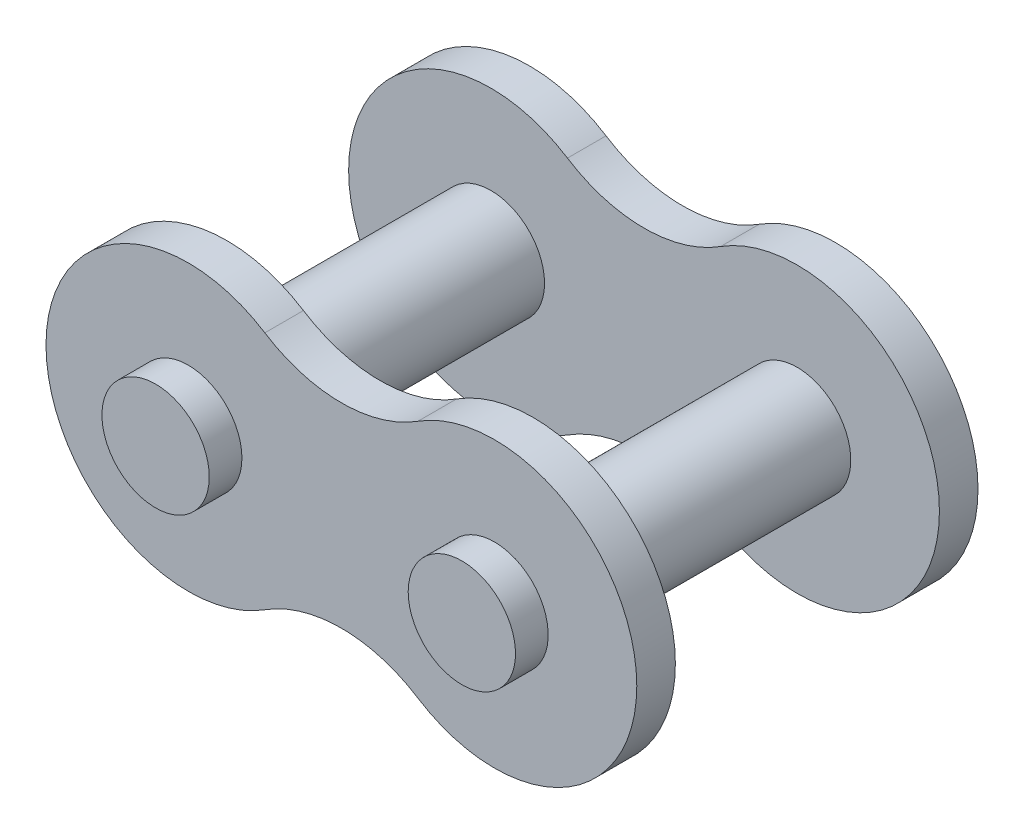
SolidWorks part; units mm, degrees
material "AISI 1020"
ref_plane "Спереди" through (0, 0, 0) normal (0, 0, 1) x (1, 0, 0)
ref_plane "Сверху" through (0, 0, 0) normal (0, 1, 0) x (1, 0, 0)
ref_plane "Справа" through (0, 0, 0) normal (1, 0, 0) x (0, 0, -1)
sketch "Эскиз1" plane through (0, 0, 0) normal (0, 0, 1) x (1, 0, 0)
  line L0 (-1000, 0) -> (49000, 0) construction
  line L1 (0, -1000) -> (0, 49000) construction
  line L2 (0, 4.0457) -> (0, -4.0457)
  circle A0 centre (-6.35, 0) radius 2.225
  arc A1 (-3.175, 4.9729) -> (-3.175, -4.9729) centre (-6.35, 0) ccw
  arc A2 (-3.175, 4.9729) -> (0, 4.0457) centre (0, 9.9457) ccw
  arc A3 (-3.175, -4.9729) -> (0, -4.0457) centre (0, -9.9457) cw
  dimension "_d2_" = 4.45
  dimension "_h2_" = 11.8
  dimension "_P" = 12.7
sketch "Эскиз2" plane through (0, 0, 0) normal (0, 1, 0) x (1, 0, 0)
  line L0 (-2392.2672, 0) -> (117221.091, 0) construction
  line L1 (0, 0) -> (0, 3.875) construction
  line L2 (0, 3.875) -> (0, 5.475) construction
  line L3 (0, 5.475) -> (0, 7.075)
  line L4 (0, 7.075) -> (0, 8.43) construction
  point P5 (0, 0)
  point P9 (0, 0)
  point P10 (0, 0)
  dimension "_b1_" = 7.75
  dimension "_T" = 1.6
  dimension "_L" = 16.86
extrude "Бобышка-Вытянуть1" add sketch "Эскиз1" against normal up to vertex (7.075 mm away) from vertex contours A2 L2 A3 A1 up to point (0, 0, -7.075) starting at point (0, 0, -5.475)
extrude "Бобышка-Вытянуть2" add sketch "Эскиз1<3>" against normal up to vertex (8.43 mm away) contours A0 up to point (0, 0, -8.43)
sketch "Эскиз1<3>" plane through (0, 0, 0) normal (0, 0, 1) x (1, 0, 0) same geometry as "Эскиз1"
mirror "Зеркальное отражение1" about plane through (0, 0, 0) normal (1, 0, 0) of bodies 104
mirror "Зеркальное отражение2" about plane through (0, 0, 0) normal (0, 0, 1) of bodies 105
